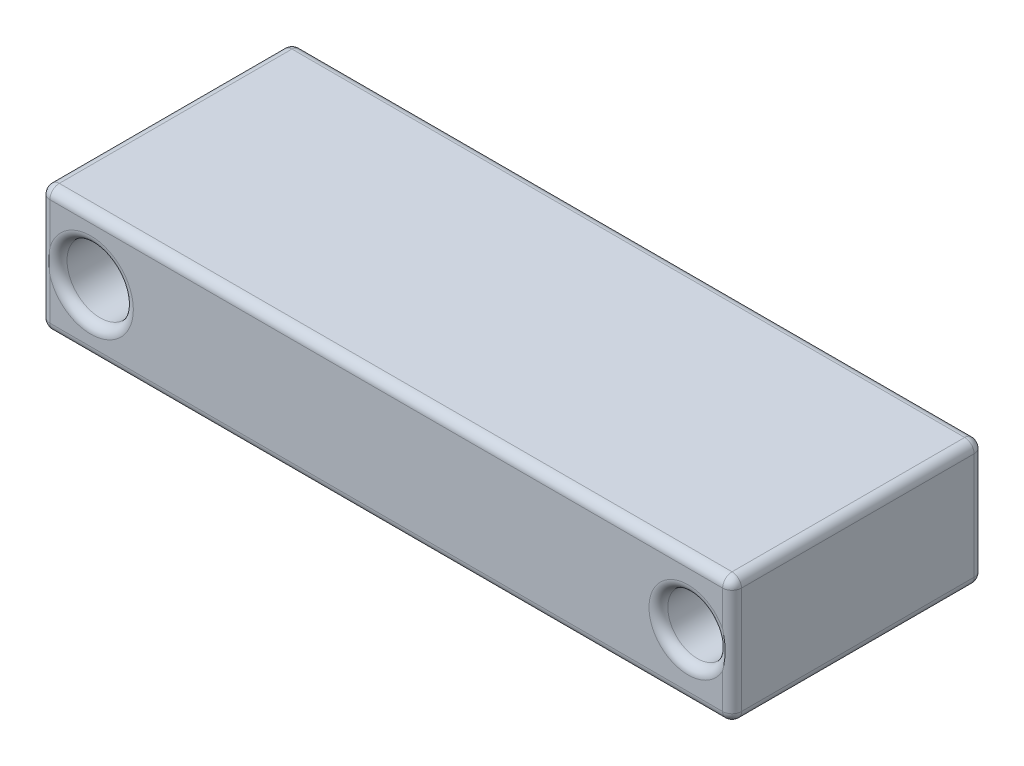
SolidWorks part; units mm, degrees
ref_plane "Front Plane" through (0, 0, 0) normal (0, 0, 1) x (1, 0, 0)
ref_plane "Top Plane" through (0, 0, 0) normal (0, 1, 0) x (1, 0, 0)
ref_plane "Right Plane" through (0, 0, 0) normal (1, 0, 0) x (0, 0, -1)
sketch "Sketch1" plane through (0, 0, 0) normal (0, 0, 1) x (1, 0, 0)
  line L1 (-95.3819, 55.5062) -> (14.6181, 55.5062)
  line L2 (-95.3819, 55.5062) -> (-95.3819, 35.5062)
  line L3 (-95.3819, 35.5062) -> (14.6181, 35.5062)
  line L4 (14.6181, 55.5062) -> (14.6181, 35.5062)
  dimension "D1" = 110
  dimension "D2" = 20
extrude "Extrude1" add sketch "Sketch1" along normal blind 40
sketch "Sketch2" plane through (0, 0, 40) normal (0, 0, 1) x (1, 0, 0)
  line L0 (14.6181, 35.5062) -> (14.6181, 55.5062) construction
  line L1 (-95.3819, 35.5062) -> (14.6181, 35.5062) construction
  circle A0 centre (-87.3819, 45.5062) radius 5.275
  circle A1 centre (7.6181, 45.5062) radius 4.714
  point P4 (14.6181, 45.5062)
  dimension "D1" = 95
  dimension "D2" = 7
  dimension "D3" = 10
  dimension "D4" = 10
extrude "Extrude2" cut sketch "Sketch2" against normal blind 110
fillet "Fillet1" radius 1.5 16 edges at (-95.3819, 35.5062, 20) (-40.3819, 35.5062, 0) (-95.3819, 45.5062, 0) (-82.1069, 45.5062, 0) (12.3321, 45.5062, 0) (14.6181, 35.5062, 20) (14.6181, 45.5062, 0) (14.6181, 55.5062, 20) (-95.3819, 55.5062, 20) (-40.3819, 55.5062, 0) (-40.3819, 55.5062, 40) (14.6181, 45.5062, 40) (-40.3819, 35.5062, 40) (-95.3819, 45.5062, 40) (-82.1069, 45.5062, 40) (12.3321, 45.5062, 40)
